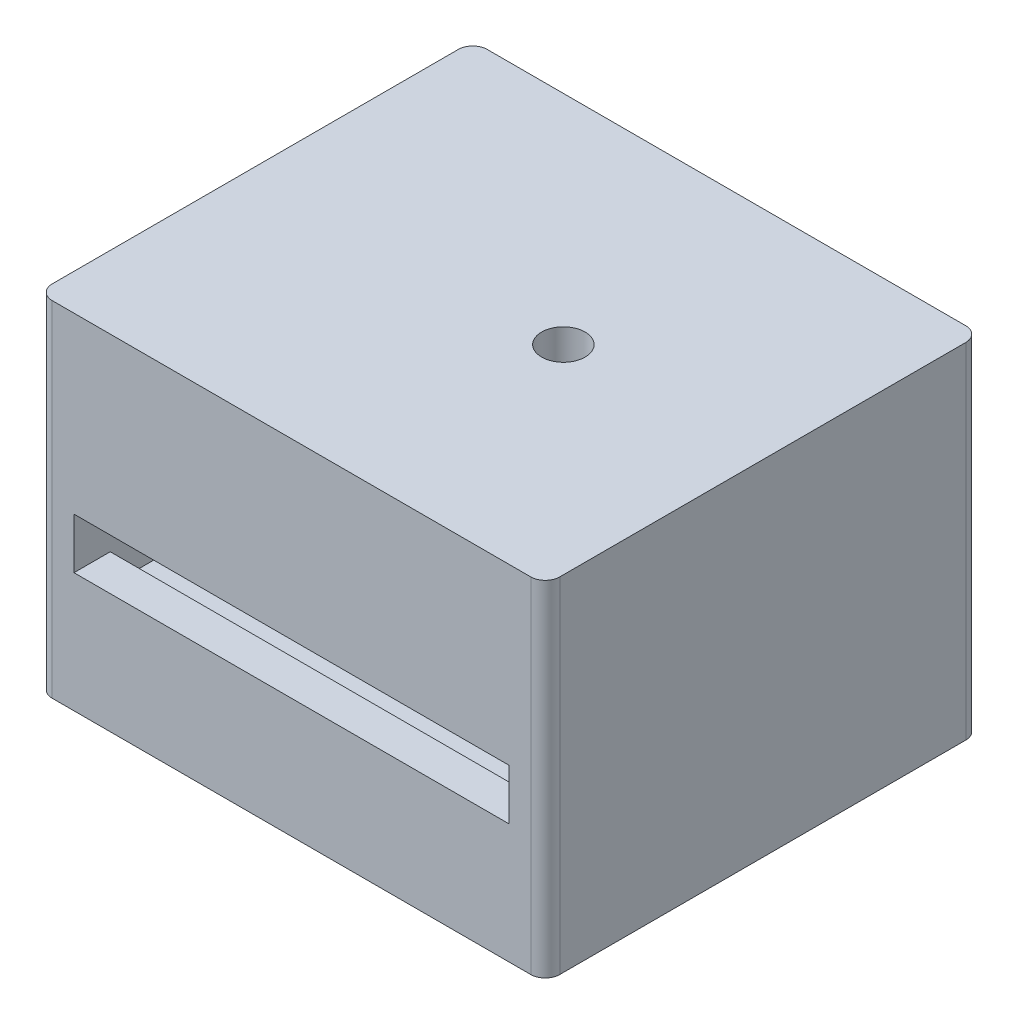
SolidWorks part; units mm, degrees
ref_plane "前视基准面" through (0, 0, 0) normal (0, 0, 1) x (1, 0, 0)
ref_plane "上视基准面" through (0, 0, 0) normal (0, 1, 0) x (1, 0, 0)
ref_plane "右视基准面" through (0, 0, 0) normal (1, 0, 0) x (0, 0, -1)
other "Configuration Table"
sketch "Sketch2" plane through (0, 0, 0) normal (0, 1, 0) x (1, 0, 0)
  line L1 (-70, -60) -> (70, -60)
  line L2 (-70, -60) -> (-70, 60)
  line L3 (-70, 60) -> (70, 60)
  line L4 (70, -60) -> (70, 60)
  point P4 (-70, 0)
  point P6 (0, 60)
  dimension "D1" = 120
  dimension "D2" = 140
extrude "BOX_EXTRUDE" add sketch "Sketch2" along normal blind 90 and the other way blind 5
sketch "Sketch3" plane through (0, 90, 0) normal (0, 1, 0) x (1, 0, 0)
  line L1 (-60, 50) -> (60, 50)
  line L2 (-60, 50) -> (-60, -50)
  line L3 (-60, -50) -> (60, -50)
  line L4 (60, 50) -> (60, -50)
  point P4 (0, 50)
  point P7 (-60, 0)
  dimension "D1" = 120
  dimension "D2" = 100
extrude "BOX_INNER_CUT" cut sketch "Sketch3" against normal blind 50 from offset 20 offset against normal yes
sketch "Sketch6" plane through (0, 90, 0) normal (0, 1, 0) x (1, 0, 0)
  line L0 (0, 30.656) -> (0, -17.5007) construction
  circle A0 centre (15, 0) radius 6
  circle A1 centre (-15, 0) radius 6
  dimension "D2" = 12
  dimension "D1" = 15
extrude "SHAFT_CUT" cut sketch "Sketch6" against normal blind 20 from offset 70 offset against normal yes
sketch "Sketch9" plane through (0, 90, 0) normal (0, 1, 0) x (1, 0, 0)
  circle A0 centre (15, 0) radius 8
  circle A2 centre (-15, 0) radius 16
  dimension "D1" = 16
  dimension "D2" = 32
extrude "BEARING_CUTS_INSIDE_BOX" cut sketch "Sketch9" against normal blind 10 from offset 70 offset against normal yes
sketch "Sketch11" plane through (0, 0, 60) normal (0, 0, 1) x (1, 0, 0)
  line L0 (-70, -5) -> (70, -5) construction
  line L1 (-60, 42) -> (60, 42)
  line L2 (-60, 42) -> (-60, 28)
  line L3 (-60, 28) -> (60, 28)
  line L4 (60, 42) -> (60, 28)
  point P4 (0, 42)
  dimension "D1" = 120
  dimension "D2" = 14
  dimension "D3" = 33
extrude "SCISSOR_CUT" cut sketch "Sketch11" against normal blind 38
sketch "Sketch12" plane through (0, 90, 0) normal (0, 1, 0) x (1, 0, 0)
  circle A0 centre (15, 0) radius 6
  dimension "D1" = 12
sketch "Sketch18" plane through (0, 90, 0) normal (0, 1, 0) x (1, 0, 0)
  circle A0 centre (-15, 0) radius 8
  dimension "D1" = 16
extrude "LEFT_BEARING_LID_CUT" cut sketch "Sketch18" against normal blind 10 from offset 10 offset against normal yes
fillet "OUTER_EDGES_FILLET" radius 4 4 edges at (-70, 42.5, -60) (70, 42.5, -60) (70, 42.5, 60) (-70, 42.5, 60)
extrude "RIGHT_BEARING_LID_CUT" cut sketch "Sketch12" against normal up to next
